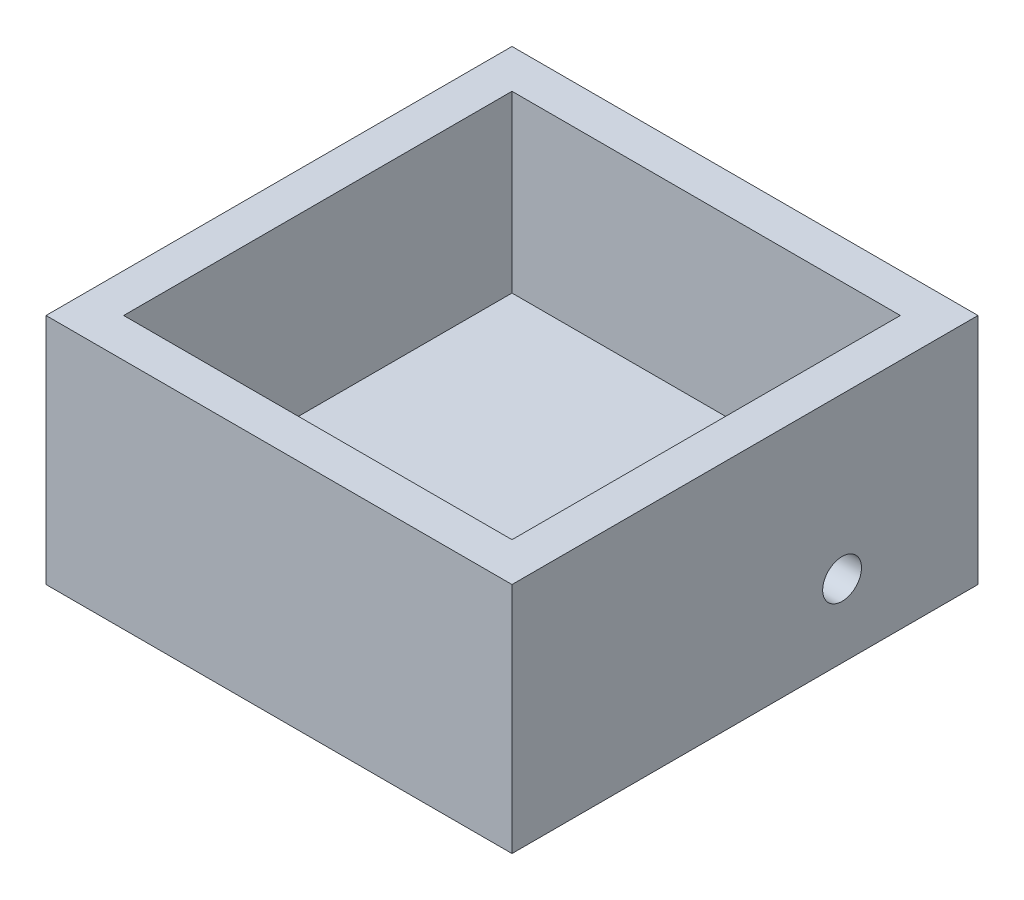
SolidWorks part; units mm, degrees
ref_plane "Front Plane" through (0, 0, 0) normal (0, 0, 1) x (1, 0, 0)
ref_plane "Top Plane" through (0, 0, 0) normal (0, 1, 0) x (1, 0, 0)
ref_plane "Right Plane" through (0, 0, 0) normal (1, 0, 0) x (0, 0, -1)
sketch "Sketch1" plane through (0, 0, 0) normal (0, 1, 0) x (1, 0, 0)
  line L1 (-24, 24) -> (24, 24)
  line L2 (-24, 24) -> (-24, -24)
  line L3 (-24, -24) -> (24, -24)
  line L4 (24, 24) -> (24, -24)
  line L5 (-20, 20) -> (20, 20)
  line L6 (-20, 20) -> (-20, -20)
  line L7 (-20, -20) -> (20, -20)
  line L8 (20, 20) -> (20, -20)
  dimension "D1" = 48
  dimension "D2" = 24
  dimension "D3" = 48
  dimension "D4" = 24
  dimension "D5" = 40
  dimension "D6" = 40
  dimension "D7" = 20
  dimension "D8" = 20
extrude "Boss-Extrude1" add sketch "Sketch1" along normal blind 24
extrude "Boss-Extrude2" add sketch "Sketch1<5>" along normal blind 4 contours L5 L8 L7 L6
sketch "Sketch1<5>" plane through (0, 0, 0) normal (0, 1, 0) x (1, 0, 0) same geometry as "Sketch1"
sketch "Sketch3" plane through (0, 4, 0) normal (0, 1, 0) x (1, 0, 0)
  line L1 (-15, 15) -> (15, 15)
  line L2 (-15, 15) -> (-15, -15)
  line L3 (-15, -15) -> (15, -15)
  line L4 (15, 15) -> (15, -15)
  dimension "D1" = 15
  dimension "D2" = 30
  dimension "D3" = 30
  dimension "D4" = 15
extrude "Boss-Extrude3" add sketch "Sketch3" along normal blind 7
sketch "Sketch4" plane through (24, 0, 0) normal (1, 0, 0) x (0, 0, -1)
  line L0 (-24, 0) -> (24, 0) construction
  line L1 (24, 24) -> (24, 0) construction
  circle A0 centre (10, 7.5) radius 2
  dimension "D1" = 4
  dimension "D2" = 7.5
  dimension "D3" = 14
extrude "Cut-Extrude1" cut sketch "Sketch4" against normal blind 25
